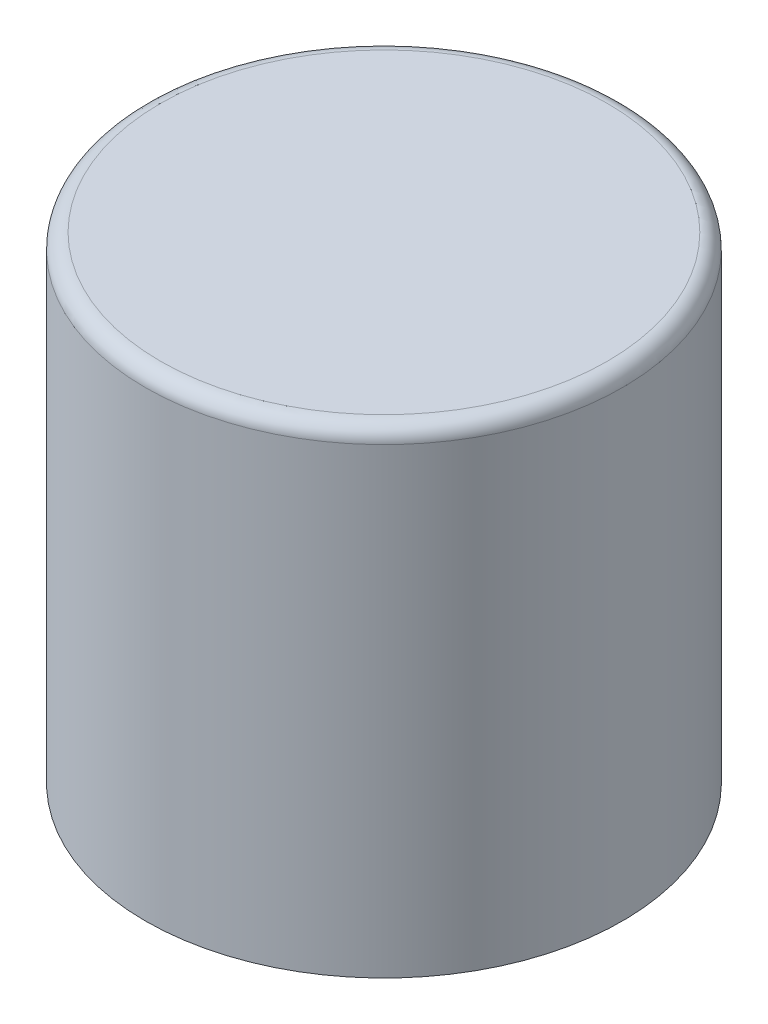
SolidWorks part; units mm, degrees
ref_plane "Front Plane" through (0, 0, 0) normal (0, 0, 1) x (1, 0, 0)
ref_plane "Top Plane" through (0, 0, 0) normal (0, 1, 0) x (1, 0, 0)
ref_plane "Right Plane" through (0, 0, 0) normal (1, 0, 0) x (0, 0, -1)
sketch "Sketch1" plane through (0, 0, 0) normal (0, 1, 0) x (1, 0, 0)
  circle A0 centre (0, 0) radius 74.5
  circle A1 centre (0, 0) radius 78.5
  dimension "D1" = 157
  dimension "D2" = 4
extrude "Boss-Extrude1" add sketch "Sketch1" along normal blind 157 contours A1
extrude "Cut-Extrude1" cut sketch "Sketch1<3>" along normal offset from surface (153 mm away) 4 contours A0 region at (0, 0, 0) up to face at (0, 157, 78.5)
sketch "Sketch1<3>" plane through (0, 0, 0) normal (0, 1, 0) x (1, 0, 0) same geometry as "Sketch1"
fillet "Fillet1" radius 5 1 edges at (0, 157, 78.5)
